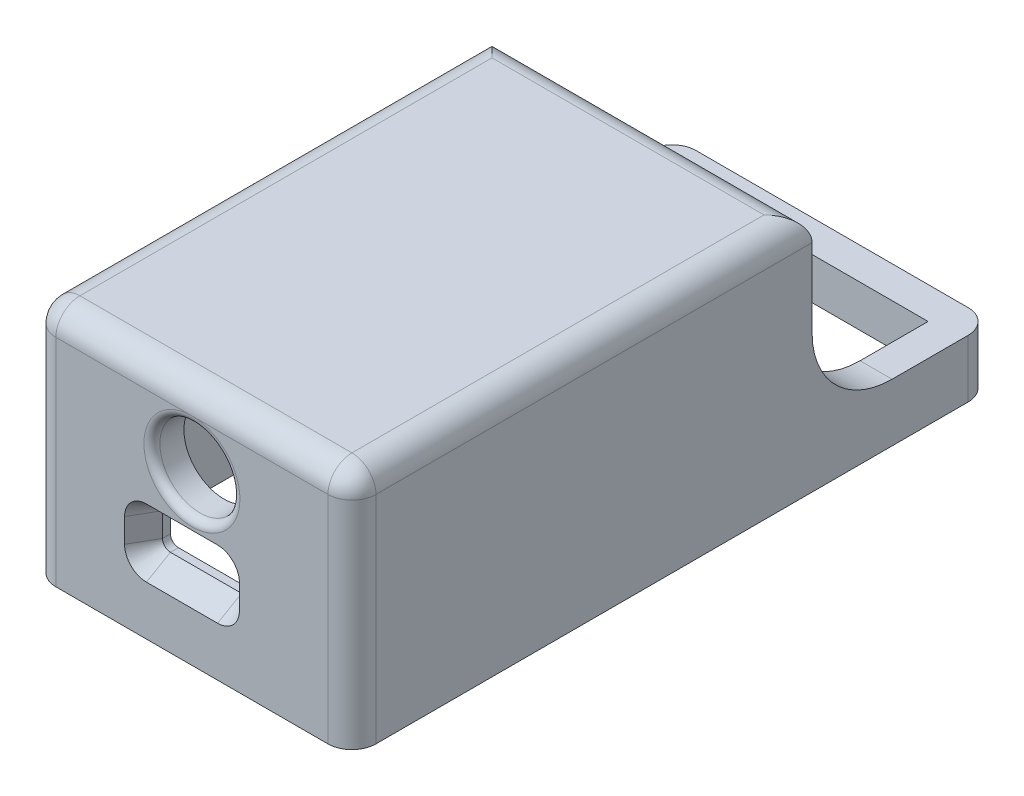
SolidWorks part; units mm, degrees
material "ABS"
ref_plane "Front Plane" through (0, 0, 0) normal (0, 0, 1) x (1, 0, 0)
ref_plane "Top Plane" through (0, 0, 0) normal (0, 1, 0) x (1, 0, 0)
ref_plane "Right Plane" through (0, 0, 0) normal (1, 0, 0) x (0, 0, -1)
sketch "Sketch1" plane through (0, 0, 0) normal (0, 0, 1) x (1, 0, 0)
  line L1 (0, 0) -> (40, 0)
  line L2 (0, 0) -> (0, 30)
  line L3 (0, 30) -> (40, 30)
  line L4 (40, 0) -> (40, 30)
  dimension "D1" = 40
  dimension "D2" = 30
extrude "Boss-Extrude1" add sketch "Sketch1" along normal blind 80
shell "Shell1" thickness 4 removed face at (20, 0, 40)
sketch "Sketch2" plane through (0, 0, 76) normal (0, 0, -1) x (-1, 0, 0)
  line L0 (-15.7364, 9.136) -> (-11.4269, 9.136) construction
  line L1 (-14.3166, 9.9804) -> (-14.3166, 7.815) construction
  line L2 (-23.2066, 10.406) -> (-23.2066, 7.815) construction
  line L11 (-13.3166, 7.8977) -> (-24.2066, 7.8977)
  line L12 (-24.2066, 7.8977) -> (-24.2066, 12.8977)
  line L13 (-13.3166, 12.8977) -> (-24.2066, 12.8977)
  line L14 (-13.3166, 7.8977) -> (-13.3166, 12.8977)
extrude "Cut-Extrude1" cut sketch "Sketch2" against normal through all
fillet "Fillet1" radius 1 4 edges at (13.3166, 7.8977, 78) (13.3166, 12.8977, 78) (24.2066, 7.8977, 78) (24.2066, 12.8977, 78)
chamfer "Chamfer1" distance 3 angle 30 8 edges at (13.3166, 10.3977, 80) (18.7616, 7.8977, 80) (13.6095, 8.1906, 80) (23.9137, 8.1906, 80) (24.2066, 10.3977, 80) (13.6095, 12.6048, 80) (23.9137, 12.6048, 80) (18.7616, 12.8977, 80) first distance on face at (13.3166, 10.3977, 78) first distance on face at (18.7616, 7.8977, 78) first distance on face at (13.7131, 8.2941, 78) first distance on face at (23.8102, 8.2941, 78) first distance on face at (24.2066, 10.3977, 78) first distance on face at (13.7131, 12.5012, 78) first distance on face at (23.8102, 12.5012, 78) first distance on face at (18.7616, 12.8977, 78)
sketch "Sketch3" plane through (0, 0, 0) normal (-1, 0, 0) x (0, 0, 1)
  line L0 (80, 30) -> (0, 30) construction
  line L1 (0, 30) -> (22.5, 30)
  line L2 (0, 30) -> (0, 7.22)
  line L3 (0, 7.22) -> (22.5, 7.22)
  line L4 (22.5, 30) -> (22.5, 7.22)
  line L5 (80, 0) -> (0, 0) construction
  dimension "D1" = 7.22
  dimension "D2" = 22.5
extrude "Cut-Extrude2" cut sketch "Sketch3" against normal through all
sketch "Sketch4" plane through (0, 0, 80) normal (0, 0, 1) x (1, 0, 0)
  line L0 (40, 30) -> (0, 30) construction
  line L1 (40, 0) -> (40, 30) construction
  line L2 (40, 30) -> (0, 30) construction
  circle A0 centre (20, 21) radius 5
  point P8 (0, 0)
  point P9 (0, 0)
  point P10 (20, 30)
  dimension "D1" = 10
  dimension "D2" = 9
extrude "Cut-Extrude3" cut sketch "Sketch4" against normal blind 5
fillet "Fillet2" radius 1 1 edges at (25, 21, 80)
fillet "Fillet3" radius 10 2 edges at (2, 7.22, 22.5) (38, 7.22, 22.5)
fillet "Fillet4" radius 3 8 edges at (40, 15, 80) (0, 15, 80) (20, 30, 80) (40, 30, 51.25) (20, 30, 22.5) (0, 30, 51.25) (40, 3.61, 0) (0, 3.61, 0)
sketch "Sketch5" plane through (0, 0, 0) normal (0, -1, 0) x (1, 0, 0)
  line L34 (4, 76) -> (4, 4)
  line L35 (4, 4) -> (36, 4)
  line L36 (36, 4) -> (36, 76)
  line L37 (36, 76) -> (4, 76)
  line L38 (38.15, 78.15) -> (1.85, 78.15)
  line L39 (1.85, 1.85) -> (38.15, 1.85)
  line L40 (1.85, 78.15) -> (1.85, 1.85)
  line L41 (38.15, 1.85) -> (38.15, 78.15)
  line L42 (36.65, 78.15) -> (3.35, 78.15)
  line L43 (3.35, 1.85) -> (36.65, 1.85)
  line L44 (1.85, 76.65) -> (1.85, 3.35)
  line L45 (38.15, 3.35) -> (38.15, 76.65)
  line L46 (1.85, 78.15) -> (1.85, 1.85) construction
  line L47 (1.85, 1.85) -> (38.15, 1.85) construction
  line L48 (38.15, 1.85) -> (38.15, 78.15) construction
  line L49 (38.15, 78.15) -> (1.85, 78.15) construction
  arc A0 (1.85, 3.35) -> (3.35, 1.85) centre (3.35, 3.35) ccw
  arc A1 (38.15, 3.35) -> (36.65, 1.85) centre (36.65, 3.35) cw
  arc A2 (36.65, 78.15) -> (38.15, 76.65) centre (36.65, 76.65) cw
  arc A3 (1.85, 76.65) -> (3.35, 78.15) centre (3.35, 76.65) cw
  dimension "D3" = 1.5
  dimension "D1" = 2.15
  dimension "D2" = 2.15
extrude "Cut-Extrude4" cut sketch "Sketch5" against normal blind 2
